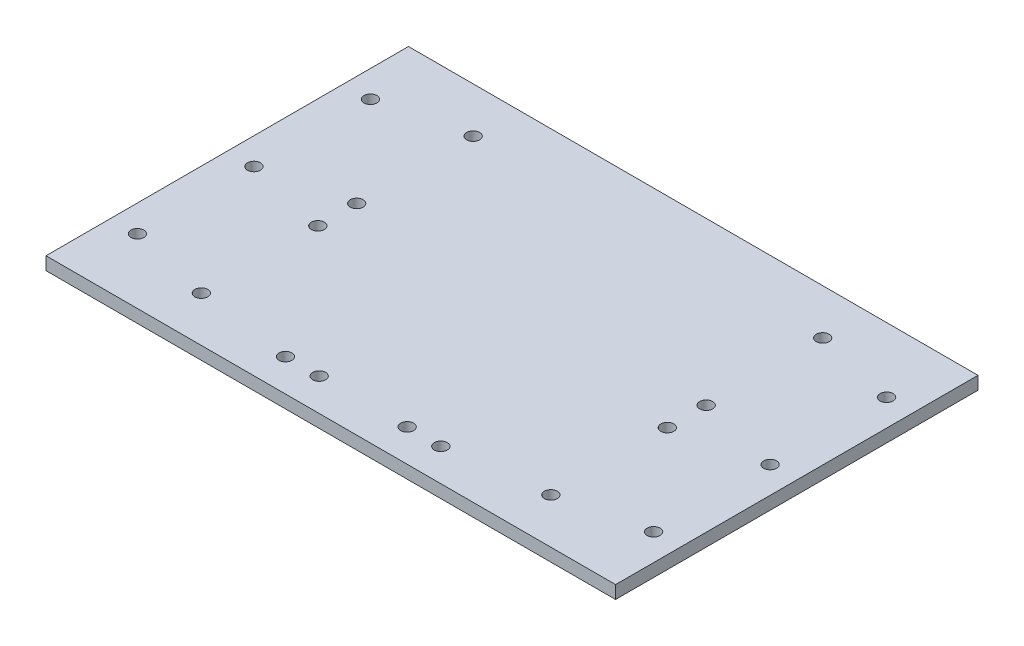
SolidWorks part; units mm, degrees
ref_plane "Front Plane" through (0, 0, 0) normal (0, 0, 1) x (1, 0, 0)
ref_plane "Top Plane" through (0, 0, 0) normal (0, 1, 0) x (1, 0, 0)
ref_plane "Right Plane" through (0, 0, 0) normal (1, 0, 0) x (0, 0, -1)
sketch "Sketch2" plane through (0, 0, 0) normal (0, 1, 0) x (1, 0, 0)
  line L0 (0, 88.9) -> (0, -88.9) construction
  line L1 (-139.7, -88.9) -> (139.7, -88.9)
  line L2 (-139.7, -88.9) -> (-139.7, 88.9)
  line L3 (-139.7, 88.9) -> (139.7, 88.9)
  line L4 (139.7, -88.9) -> (139.7, 88.9)
  line L5 (-139.7, 0) -> (139.7, 0) construction
  circle A11 centre (-21.59, -73.025) radius 3.175
  circle A18 centre (-38.1, -73.025) radius 3.175
  circle A19 centre (38.1, -73.025) radius 3.175
  circle A20 centre (21.59, -73.025) radius 3.175
  dimension "D11" = 21.59
  dimension "D14" = 6.35
  dimension "D15" = 15.875
  dimension "D12" = 6.35
  dimension "D1" = 88.9
  dimension "D2" = 177.8
  dimension "D3" = 279.4
  dimension "D4" = 139.7
  dimension "D13" = 38.1
extrude "Boss-Extrude1" add sketch "Sketch2" along normal blind 6.35
sketch "Sketch3" plane through (0, 6.35, 0) normal (0, 1, 0) x (1, 0, 0)
  line L0 (-126.619, 57.15) -> (-126.619, -57.15) construction
  line L1 (-126.619, 0) -> (126.619, 0) construction
  line L2 (126.619, 57.15) -> (126.619, -57.15) construction
  circle A6 centre (-126.619, 57.15) radius 3.175
  circle A7 centre (-126.619, -57.15) radius 3.175
  circle A8 centre (126.619, -57.15) radius 3.175
  circle A9 centre (126.619, 0) radius 3.175
  circle A10 centre (126.619, 57.15) radius 3.175
  circle A11 centre (-126.619, 0) radius 3.175
  point P0 (0, 0)
  dimension "D3" = 6.35
  dimension "D1" = 253.238
  dimension "D2" = 114.3
extrude "Cut-Extrude1" cut sketch "Sketch3" against normal through all
sketch "Sketch4" plane through (0, 0, 0) normal (0, -1, 0) x (1, 0, 0)
  line L0 (85.725, 0) -> (-85.725, 0) construction
  line L1 (-85.725, -9.525) -> (-85.725, 9.525) construction
  line L2 (-85.725, 9.525) -> (-85.725, 66.675) construction
  line L3 (0, 0) -> (0, 39.5223) construction
  line L4 (85.725, -9.525) -> (85.725, 9.525) construction
  line L5 (85.725, 9.525) -> (85.725, 66.675) construction
  line L6 (85.725, -9.525) -> (85.725, -66.675) construction
  line L7 (-85.725, -9.525) -> (-85.725, -66.675) construction
  circle A0 centre (-85.725, 66.675) radius 3.175
  circle A2 centre (-85.725, -66.675) radius 3.175
  circle A3 centre (85.725, -66.675) radius 3.175
  circle A4 centre (85.725, -9.525) radius 3.175
  circle A5 centre (85.725, 9.525) radius 3.175
  circle A6 centre (85.725, 66.675) radius 3.175
  circle A7 centre (-85.725, 9.525) radius 3.175
  circle A8 centre (-85.725, -9.525) radius 3.175
  dimension "D4" = 6.35
  dimension "D1" = 85.725
  dimension "D2" = 9.525
  dimension "D3" = 57.15
extrude "Cut-Extrude2" cut sketch "Sketch4" against normal through all
